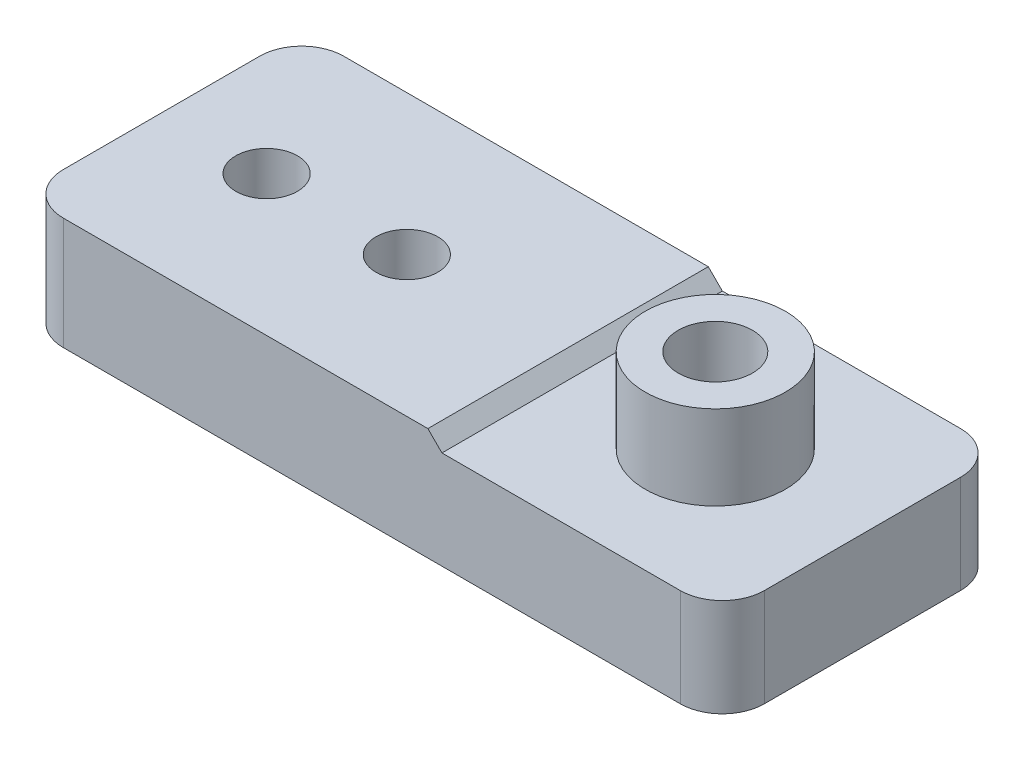
SolidWorks part; units mm, degrees
ref_plane "Alzado" through (0, 0, 0) normal (0, 0, 1) x (1, 0, 0)
ref_plane "Planta" through (0, 0, 0) normal (0, 1, 0) x (1, 0, 0)
ref_plane "Vista lateral" through (0, 0, 0) normal (1, 0, 0) x (0, 0, -1)
sketch "Croquis1" plane through (0, 0, 0) normal (0, 1, 0) x (1, 0, 0)
  line L0 (-22, -10) -> (22, -10)
  line L1 (-22, 10) -> (22, 10)
  line L2 (-25, 7) -> (-25, -7)
  line L4 (25, 7) -> (25, -7)
  line L5 (0, 10) -> (0, -10) construction
  line L6 (0, 0) -> (14.5, 0) construction
  line L7 (0, 0) -> (-7.5, 0) construction
  line L8 (-17.5, 0) -> (-7.5, 0) construction
  circle A1 centre (-17.5, 0) radius 2.2
  circle A2 centre (-7.5, 0) radius 2.2
  circle A3 centre (14.5, 0) radius 2.65
  circle A4 centre (14.5, 0) radius 5
  arc A5 (22, -10) -> (25, -7) centre (22, -7) ccw
  arc A6 (25, 7) -> (22, 10) centre (22, 7) ccw
  arc A7 (-22, -10) -> (-25, -7) centre (-22, -7) cw
  arc A8 (-25, 7) -> (-22, 10) centre (-22, 7) cw
  dimension "D1" = 14.5
  dimension "D2" = 7.5
  dimension "D3" = 3
  dimension "D4" = 50
  dimension "D6" = 5.3
  dimension "D7" = 10
  dimension "D9" = 4.4
  dimension "D10" = 4.4
  dimension "D5" = 20
  dimension "D8" = 10
extrude "Saliente-Extruir1" add sketch "Croquis1" along normal blind 8 contours A8 L2 A7 L0 A5 L4 A6 L1 A4 A2 A1 region at (-0.8589, 0, 0)
sketch "Croquis2" plane through (0, 0, 10) normal (0, 0, 1) x (1, 0, 0)
  line L0 (4, 8) -> (4, 0) construction
  line L1 (-22, 8) -> (22, 8) construction
  line L2 (4, 8) -> (5.0041, 6.9959)
  line L3 (5.0041, 6.9959) -> (27.295, 6.9959)
  line L4 (4, 8) -> (27.295, 8)
  line L5 (27.295, 8) -> (27.295, 6.9959)
  line L6 (-22, 0) -> (22, 0) construction
  line L7 (25, 0) -> (4, 0) construction
  dimension "D1" = 315
  dimension "D2" = 22.2909
  dimension "D3" = 1.42
  dimension "D4" = 21
extrude "Cortar-Extruir1" cut sketch "Croquis2" against normal blind 26
extrude "Saliente-Extruir2" add sketch "Croquis1<3>" along normal blind 13 contours A4 A3 region at (9.6414, 0, 0)
sketch "Croquis1<3>" plane through (0, 0, 0) normal (0, 1, 0) x (1, 0, 0) same geometry as "Croquis1"
